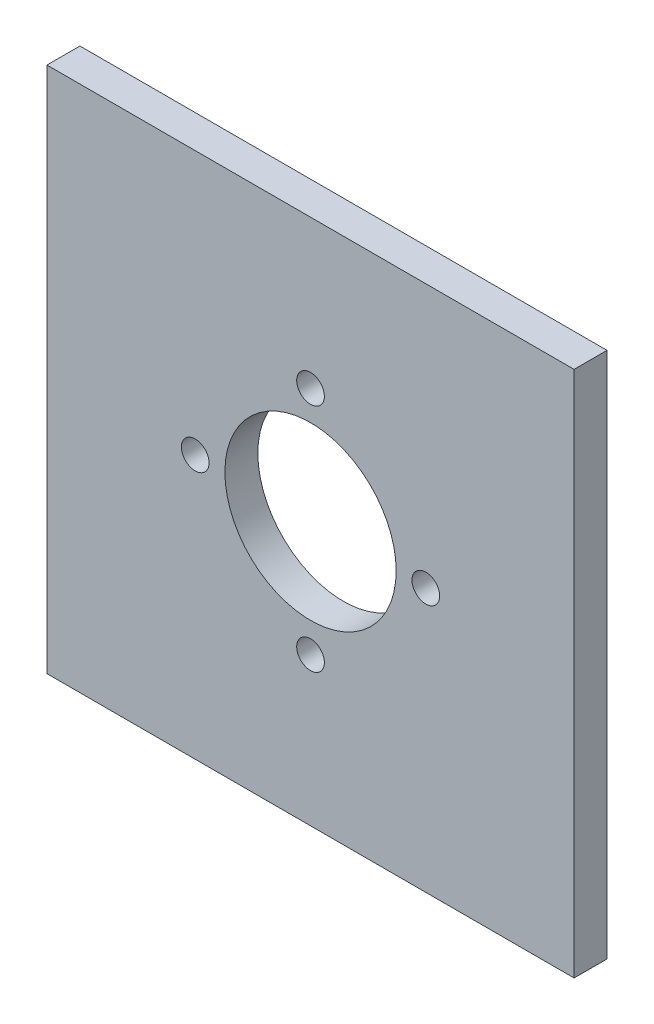
SolidWorks part; units mm, degrees
ref_plane "前视基准面" through (0, 0, 0) normal (0, 0, 1) x (1, 0, 0)
ref_plane "上视基准面" through (0, 0, 0) normal (0, 1, 0) x (1, 0, 0)
ref_plane "右视基准面" through (0, 0, 0) normal (1, 0, 0) x (0, 0, -1)
sketch "草图1" plane through (0, 0, 0) normal (0, 0, 1) x (1, 0, 0)
  line L1 (-40, 40) -> (40, 40)
  line L2 (-40, 40) -> (-40, -40)
  line L3 (-40, -40) -> (40, -40)
  line L4 (40, 40) -> (40, -40)
  line L5 (-40, 40) -> (40, -40) construction
  line L6 (-40, -40) -> (40, 40) construction
  circle A0 centre (0, 0) radius 13
  point P0 (0, 0)
  dimension "D3" = 26
  dimension "D1" = 80
  dimension "D2" = 80
extrude "凸台-拉伸1" add sketch "草图1" along normal blind 5
sketch "草图2" plane through (0, 0, 5) normal (0, 0, 1) x (1, 0, 0)
  line L0 (-17.5, 0) -> (0, 17.5) construction
  line L1 (-17.5, 0) -> (0, -17.5) construction
  line L2 (0, 17.5) -> (17.5, 0) construction
  line L3 (0, -17.5) -> (17.5, 0) construction
  line L4 (-17.5, 0) -> (17.5, 0) construction
  line L5 (0, 17.5) -> (0, -17.5) construction
  line L6 (40, 40) -> (-40, 40) construction
  circle A0 centre (0, 17.5) radius 2.1
  circle A1 centre (17.5, 0) radius 2.1
  circle A2 centre (-17.5, 0) radius 2.1
  circle A3 centre (0, -17.5) radius 2.1
  point P1 (0, 0)
  dimension "D2" = 4.2
  dimension "D3" = 4.2
  dimension "D4" = 4.2
  dimension "D5" = 4.2
  dimension "D1" = 35
extrude "切除-拉伸1" cut sketch "草图2" against normal blind 5
